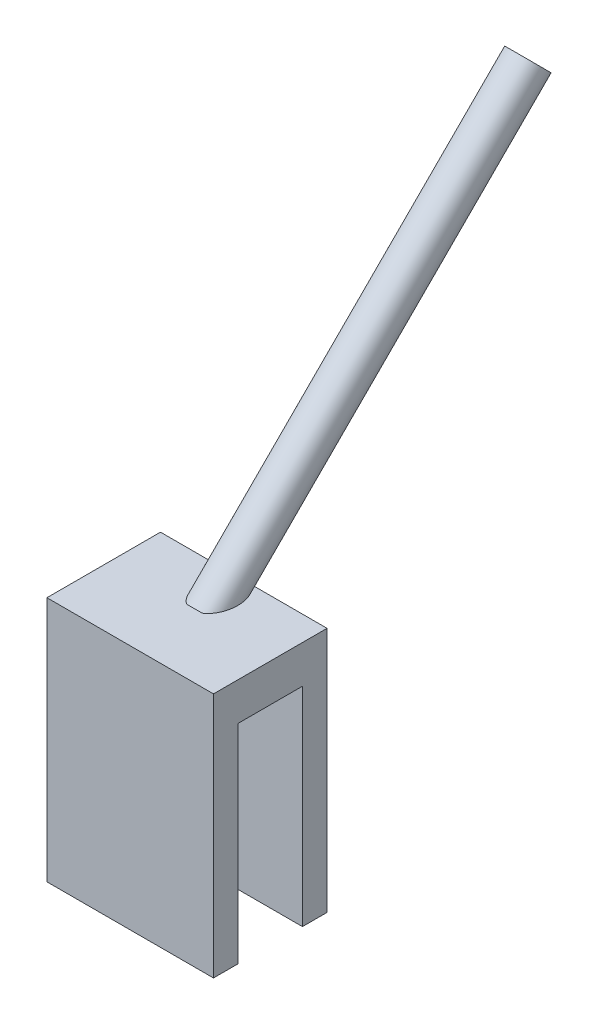
SolidWorks part; units mm, degrees
ref_plane "Front Plane" through (0, 0, 0) normal (0, 0, 1) x (1, 0, 0)
ref_plane "Top Plane" through (0, 0, 0) normal (0, 1, 0) x (1, 0, 0)
ref_plane "Right Plane" through (0, 0, 0) normal (1, 0, 0) x (0, 0, -1)
sketch "Sketch1" plane through (0, 0, 0) normal (0, 1, 0) x (1, 0, 0)
  line L1 (-22, -15) -> (22, -15)
  line L2 (-22, -15) -> (-22, 15)
  line L3 (-22, 15) -> (22, 15)
  line L4 (22, -15) -> (22, 15)
  line L5 (-22, -15) -> (22, 15) construction
  line L6 (-22, 15) -> (22, -15) construction
  point P0 (0, 0)
  dimension "D1" = 30
  dimension "D2" = 44
extrude "Boss-Extrude1" add sketch "Sketch1" along normal blind 65
sketch "Sketch2" plane through (22, 0, 0) normal (1, 0, 0) x (0, 0, -1)
  line L0 (-15, 0) -> (15, 0) construction
  line L1 (-8.5, 0) -> (8.5, 0)
  line L2 (-8.5, 0) -> (-8.5, 55)
  line L3 (-8.5, 55) -> (8.5, 55)
  line L4 (8.5, 0) -> (8.5, 55)
  line L5 (-15, 65) -> (-15, 0) construction
  line L6 (15, 65) -> (15, 0) construction
  dimension "D1" = 6.5
  dimension "D2" = 6.5
  dimension "D3" = 55
extrude "Cut-Extrude1" cut sketch "Sketch2" against normal through all both and the other way through all
sketch3d "3DSketch1"
  point P0 (-2.8715, 51.9749, -15)
ref_plane "Plane1" through (0, 33.4875, -33.4875) normal (0, 0.7071, -0.7071) x (0, -0.7071, -0.7071)
sketch "Sketch3" plane through (0, 33.4875, -33.4875) normal (0, 0.7071, -0.7071) x (0, -0.7071, -0.7071)
  circle A0 centre (-40, 0) radius 5
  dimension "D1" = 10
  dimension "D2" = 40
extrude "Boss-Extrude2" add sketch "Sketch3" along normal blind 120
extrude "Boss-Extrude3" add sketch "Sketch3<2>" along normal blind 120
sketch "Sketch3<2>" plane through (0, 33.4875, -33.4875) normal (0, 0.7071, -0.7071) x (0, -0.7071, -0.7071) same geometry as "Sketch3"
